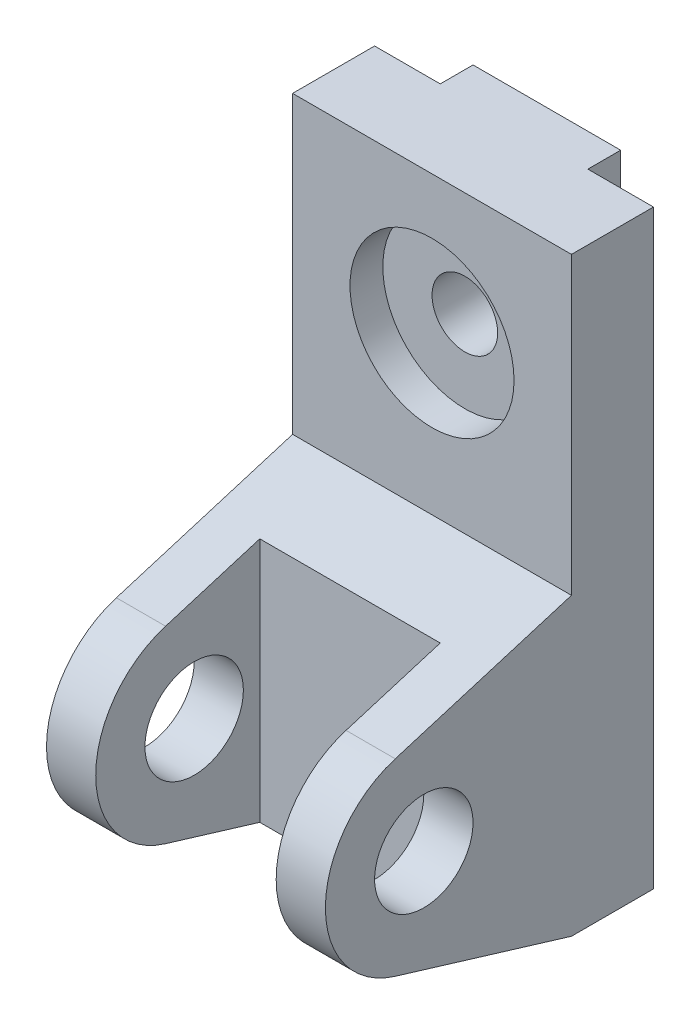
SolidWorks part; units mm, degrees
ref_plane "Front Plane" through (0, 0, 0) normal (0, 0, 1) x (1, 0, 0)
ref_plane "Top Plane" through (0, 0, 0) normal (0, 1, 0) x (1, 0, 0)
ref_plane "Right Plane" through (0, 0, 0) normal (1, 0, 0) x (0, 0, -1)
sketch "Sketch1" plane through (0, 0, 0) normal (1, 0, 0) x (0, 0, -1)
  line L0 (0, 180) -> (0, 0)
  line L1 (0, 0) -> (-25, 0)
  line L2 (-25, 0) -> (-78.7083, 16.2917)
  line L3 (0, 180) -> (-25, 180)
  line L4 (-25, 180) -> (-25, 90)
  line L5 (-25, 90) -> (-78.7083, 73.7083)
  line L6 (-100, 45) -> (0, 45) construction
  line L7 (-70, 45) -> (-70, 76.3498) construction
  circle A0 centre (-70, 45) radius 15
  arc A1 (-78.7083, 73.7083) -> (-78.7083, 16.2917) centre (-70, 45) ccw
  dimension "D3" = 30
  dimension "D4" = 60
  dimension "D1" = 180
  dimension "D2" = 25
  dimension "D5" = 70
  dimension "D6" = 45
  dimension "D7" = 90
extrude "Boss-Extrude1" add sketch "Sketch1" against normal blind 85
ref_axis "Axis1" through (-85, 45, 70) along (1, 0, 0)
sketch "Sketch2" plane through (0, 0, 0) normal (0, -1, 0) x (1, 0, 0)
  line L0 (-85, 0) -> (0, 0) construction
  line L1 (-70, 111.6126) -> (-15, 111.6126)
  line L2 (-70, 111.6126) -> (-70, 50)
  line L3 (-70, 50) -> (-15, 50)
  line L4 (-15, 111.6126) -> (-15, 50)
  line L5 (-65, 0) -> (-20, 0)
  line L6 (-65, 0) -> (-65, -10)
  line L7 (-65, -10) -> (-20, -10)
  line L8 (-20, 0) -> (-20, -10)
  line L9 (0, 78.7083) -> (0, 25) construction
  line L11 (-85, 70) -> (0, 70) construction
  line L12 (0, 25) -> (0, 0) construction
  dimension "D1" = 55
  dimension "D2" = 15
  dimension "D3" = 20
  dimension "D4" = 45
  dimension "D5" = 10
  dimension "D6" = 20
extrude "Cut-Extrude1" cut sketch "Sketch2" against normal blind 85 contours L2 L1 L4 L3
sketch "Sketch3" plane through (0, 0, 0) normal (0, -1, 0) x (1, 0, 0)
  line L0 (-85, 0) -> (0, 0) construction
  line L1 (-65, 0) -> (-20, 0)
  line L2 (-65, 0) -> (-65, -10)
  line L3 (-65, -10) -> (-20, -10)
  line L4 (-20, 0) -> (-20, -10)
  line L5 (0, 25) -> (0, 0) construction
  dimension "D1" = 20
  dimension "D2" = 45
  dimension "D3" = 10
extrude "Boss-Extrude2" add sketch "Sketch3" against normal up to surface (180 mm away) up to face at (-42.5, 180, 12.5)
hole_wizard "CBORE for 1/4 Binding Head Machine Screw1" positions "Sketch4" profile "Sketch5" counterbore size "1/4" standard "ANSI Inch" end condition through all
sketch "Sketch4" plane through (0, 0, 25) normal (0, 0, 1) x (1, 0, 0)
  line L0 (-85, 180) -> (0, 180) construction
  line L2 (-42.5, 180) -> (-42.5, 0) construction
  line L3 (-85, 0) -> (0, 0) construction
  point P0 (-42.5, 138)
  point P13 (0, 0)
  dimension "D1" = 42
sketch "Sketch5" plane through (-42.5, 138, 25) normal (1, 0, 0) x (0, -1, 0)
  line L0 (0, 0) -> (0, 35)
  line L1 (0, 35) -> (10, 35)
  line L3 (10, 35) -> (10, 10)
  line L4 (10, 10) -> (25, 10)
  line L5 (25, 10) -> (25, 0)
  line L7 (25, 0) -> (0, 0)
  line L11 (0, -6.35) -> (0, 107.95) construction
  dimension "Thru Hole Dia." = 20
  dimension "Thru Hole Depth" = 35
  dimension "C'Bore Dia." = 50
  dimension "C'Bore Depth" = 10
